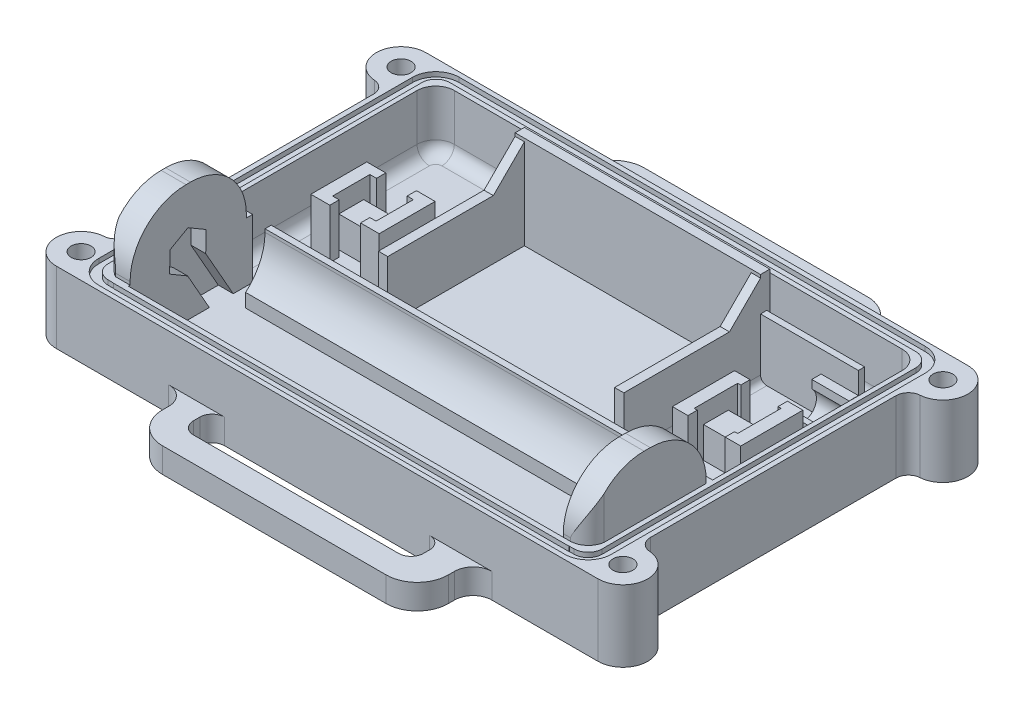
SolidWorks part; units mm, degrees
ref_plane "Спереди" through (0, 0, 0) normal (0, 0, 1) x (1, 0, 0)
ref_plane "Сверху" through (0, 0, 0) normal (0, 1, 0) x (1, 0, 0)
ref_plane "Справа" through (0, 0, 0) normal (1, 0, 0) x (0, 0, -1)
sketch "Эскиз1" plane through (0, 0, 0) normal (0, 1, 0) x (1, 0, 0)
  line L1 (-35, 9.5) -> (35, 9.5)
  line L2 (-35, 9.5) -> (-35, -9.5)
  line L3 (-35, -9.5) -> (35, -9.5)
  line L4 (35, 9.5) -> (35, -9.5)
  line L5 (-35, 9.5) -> (35, -9.5) construction
  line L6 (-35, -9.5) -> (35, 9.5) construction
  line L7 (-18.25, 37.5) -> (18.25, 37.5)
  line L8 (-18.25, 37.5) -> (-18.25, 10.5)
  line L9 (-18.25, 10.5) -> (18.25, 10.5)
  line L10 (18.25, 37.5) -> (18.25, 10.5)
  line L11 (-18.25, 37.5) -> (18.25, 10.5) construction
  line L12 (-18.25, 10.5) -> (18.25, 37.5) construction
  line L13 (-35, 44) -> (35, 44)
  line L14 (-35, 44) -> (-35, 38.5)
  line L15 (-35, 38.5) -> (35, 38.5)
  line L16 (35, 44) -> (35, 38.5)
  line L17 (-35, 44) -> (35, 38.5) construction
  line L18 (-35, 38.5) -> (35, 44) construction
  line L23 (-42, -12.5) -> (42, -12.5)
  line L24 (-42, -12.5) -> (-42, 47)
  line L25 (-42, 47) -> (42, 47)
  line L26 (42, -12.5) -> (42, 47)
  point P0 (0, 0)
  point P6 (0, 24)
  point P11 (0, 38.5)
  point P12 (0, 9.5)
  point P13 (0, 10.5)
  point P14 (0, 41.25)
  point P19 (0, 37.5)
  point P20 (-35, 0)
  point P25 (35, 0)
  point P26 (0, -9.5)
  point P27 (0, 44)
  dimension "D1" = 70
  dimension "D2" = 19
  dimension "D3" = 36.5
  dimension "D4" = 27
  dimension "D5" = 1
  dimension "D6" = 5.5
  dimension "D7" = 1
  dimension "D8" = 70
  dimension "D9" = 7
  dimension "D10" = 3
  dimension "D11" = 3
  dimension "D12" = 7
sketch "Эскиз7" plane through (0, 0, 0) normal (0, 1, 0) x (1, 0, 0)
  line L0 (-42.0364, 37.0159) -> (-42.0364, -2.5159)
  line L1 (-42, 47) -> (42, 47)
  line L2 (0, -12.5) -> (0, 47) construction
  line L3 (-42, -12.5) -> (42, -12.5)
  line L4 (42.0364, 37.0159) -> (42.0364, -2.5159)
  line L5 (-43.6, 47) -> (-42, 47)
  line L6 (36, 17.25) -> (-42.0364, 17.25) construction
  line L7 (43.6, 47) -> (42, 47)
  line L8 (43.6, -12.5) -> (42, -12.5)
  line L9 (-43.6, -12.5) -> (-42, -12.5)
  circle A0 centre (-43.6, 43) radius 1.6
  arc A1 (-43.6, 47) -> (-43.8909, 39.0106) centre (-43.6, 43) ccw
  arc A2 (-43.8909, 39.0106) -> (-42.0364, 37.0159) centre (-44.0364, 37.0159) cw
  arc A3 (43.8909, 39.0106) -> (42.0364, 37.0159) centre (44.0364, 37.0159) ccw
  arc A4 (43.6, 47) -> (43.8909, 39.0106) centre (43.6, 43) cw
  circle A5 centre (43.6, 43) radius 1.6
  circle A6 centre (43.6, -8.5) radius 1.6
  arc A7 (43.6, -12.5) -> (43.8909, -4.5106) centre (43.6, -8.5) ccw
  arc A8 (43.8909, -4.5106) -> (42.0364, -2.5159) centre (44.0364, -2.5159) cw
  arc A9 (-43.8909, -4.5106) -> (-42.0364, -2.5159) centre (-44.0364, -2.5159) ccw
  arc A10 (-43.6, -12.5) -> (-43.8909, -4.5106) centre (-43.6, -8.5) cw
  circle A11 centre (-43.6, -8.5) radius 1.6
  dimension "D1" = 3.2
  dimension "D2" = 8
  dimension "D3" = 2
extrude "Бобышка-Вытянуть4" add sketch "Эскиз7" along normal blind 2
sketch "Эскиз8" plane through (0, 2, 0) normal (0, 1, 0) x (1, 0, 0)
  line L0 (-43.6, -12.5) -> (43.6, -12.5) construction
  line L3 (43.6, 47) -> (-43.6, 47) construction
  line L4 (-43.6, -12.5) -> (43.6, -12.5)
  line L5 (42.0364, -2.5159) -> (42.0364, 37.0159)
  line L6 (-42.0364, -2.5159) -> (-42.0364, 37.0159)
  line L7 (43.6, 47) -> (-43.6, 47)
  line L9 (-36.0364, 44) -> (36.0364, 44)
  line L10 (-39.0364, 41) -> (-39.0364, -6.5)
  line L11 (-36.0364, -9.5) -> (36.0364, -9.5)
  line L12 (39.0364, 41) -> (39.0364, -6.5)
  arc A0 (42.0364, -2.5159) -> (43.8909, -4.5106) centre (44.0364, -2.5159) ccw construction
  circle A1 centre (43.6, -8.5) radius 1.6 construction
  arc A2 (43.6, -12.5) -> (43.8909, -4.5106) centre (43.6, -8.5) ccw construction
  circle A3 centre (-43.6, -8.5) radius 1.6 construction
  arc A4 (-43.8909, -4.5106) -> (-43.6, -12.5) centre (-43.6, -8.5) ccw construction
  arc A5 (-43.8909, -4.5106) -> (-42.0364, -2.5159) centre (-44.0364, -2.5159) ccw construction
  circle A6 centre (-43.6, 43) radius 1.6 construction
  circle A7 centre (43.6, 43) radius 1.6 construction
  arc A8 (43.8909, 39.0106) -> (42.0364, 37.0159) centre (44.0364, 37.0159) ccw construction
  arc A9 (43.8909, 39.0106) -> (43.6, 47) centre (43.6, 43) ccw construction
  arc A10 (-42.0364, 37.0159) -> (-43.8909, 39.0106) centre (-44.0364, 37.0159) ccw construction
  arc A11 (-43.6, 47) -> (-43.8909, 39.0106) centre (-43.6, 43) ccw construction
  arc A12 (42.0364, -2.5159) -> (43.8909, -4.5106) centre (44.0364, -2.5159) ccw
  circle A13 centre (43.6, -8.5) radius 1.6
  arc A14 (43.6, -12.5) -> (43.8909, -4.5106) centre (43.6, -8.5) ccw
  circle A15 centre (-43.6, -8.5) radius 1.6
  arc A16 (-43.8909, -4.5106) -> (-43.6, -12.5) centre (-43.6, -8.5) ccw
  arc A17 (-43.8909, -4.5106) -> (-42.0364, -2.5159) centre (-44.0364, -2.5159) ccw
  circle A18 centre (-43.6, 43) radius 1.6
  circle A19 centre (43.6, 43) radius 1.6
  arc A20 (43.8909, 39.0106) -> (42.0364, 37.0159) centre (44.0364, 37.0159) ccw
  arc A21 (43.8909, 39.0106) -> (43.6, 47) centre (43.6, 43) ccw
  arc A22 (-42.0364, 37.0159) -> (-43.8909, 39.0106) centre (-44.0364, 37.0159) ccw
  arc A23 (-43.6, 47) -> (-43.8909, 39.0106) centre (-43.6, 43) ccw
  arc A24 (36.0364, 44) -> (39.0364, 41) centre (36.0364, 41) cw
  arc A25 (36.0364, -9.5) -> (39.0364, -6.5) centre (36.0364, -6.5) ccw
  arc A26 (-39.0364, -6.5) -> (-36.0364, -9.5) centre (-36.0364, -6.5) ccw
  arc A27 (-36.0364, 44) -> (-39.0364, 41) centre (-36.0364, 41) ccw
  point P38 (0, 44)
  dimension "D5" = 3
  dimension "D1" = 3
  dimension "D2" = 3
  dimension "D3" = 3
  dimension "D4" = 3
extrude "Бобышка-Вытянуть5" add sketch "Эскиз8" along normal blind 9.5
sketch "Эскиз9" plane through (0, 11.5, 0) normal (0, 1, 0) x (1, 0, 0)
  line L0 (-42, 47) -> (42, 47) construction
  line L1 (-37.5, -11) -> (37.5, -11)
  line L2 (-40.5, -8) -> (-40.5, 42.5)
  line L3 (-37.5, 45.5) -> (37.5, 45.5)
  line L4 (40.5, -8) -> (40.5, 42.5)
  line L5 (-42, -12.5) -> (-42, 47) construction
  line L6 (42, -12.5) -> (42, 47) construction
  line L7 (-42, -12.5) -> (42, -12.5) construction
  arc A0 (-37.5, -11) -> (-40.5, -8) centre (-37.5, -8) cw
  arc A1 (-40.5, 42.5) -> (-37.5, 45.5) centre (-37.5, 42.5) cw
  arc A2 (37.5, 45.5) -> (40.5, 42.5) centre (37.5, 42.5) cw
  arc A3 (37.5, -11) -> (40.5, -8) centre (37.5, -8) ccw
  point P4 (0, 45.5)
  point P7 (-40.5, 17.25)
  point P10 (0, -11)
  dimension "D5" = 3
  dimension "D1" = 1.5
  dimension "D2" = 1.5
  dimension "D3" = 1.5
  dimension "D4" = 1.5
extrude "Вырез-Вытянуть-Тонкостенный1" cut sketch "Эскиз9" against normal blind 0.75 thin thin type mid plane wall 1.5
sketch "Эскиз10" plane through (0, 2, 0) normal (0, 1, 0) x (1, 0, 0)
  line L0 (-39.75, 42.5) -> (-39.75, -8) construction
  line L1 (-35, 9.5) -> (35, 9.5)
  line L2 (-35, 9.5) -> (-35, -9.5)
  line L3 (-35, -9.5) -> (35, -9.5)
  line L4 (35, 9.5) -> (35, -9.5)
  line L5 (-39.75, 10.5) -> (39.75, 10.5)
  line L6 (-39.75, 10.5) -> (-39.75, -7.6379)
  line L7 (-36.6026, -10.2814) -> (36.7169, -10.2814)
  line L8 (39.75, 10.5) -> (39.75, -7.2482)
  line L9 (36.7169, -10.2814) -> (39.75, -7.2482)
  line L10 (-36.6026, -10.2814) -> (-39.75, -7.6379)
extrude "Бобышка-Вытянуть6" add sketch "Эскиз10" along normal up to surface (9.5 mm away) up to face at (0, 11.5, -17.25)
sketch "Эскиз11" plane through (0, 11.5, 0) normal (0, 1, 0) x (1, 0, 0)
  line L1 (-35, 9.5) -> (-39, 9.5)
  line L2 (-35, 9.5) -> (-35, -9.216)
  line L3 (-35, -9.216) -> (-39, -9.216)
  line L4 (-39, 9.5) -> (-39, -9.216)
  line L5 (35, 9.5) -> (39, 9.5)
  line L6 (35, 9.5) -> (35, -9.4965)
  line L7 (35, -9.4965) -> (39, -9.4965)
  line L8 (39, 9.5) -> (39, -9.4965)
  point P5 (-39, 0.142)
  point P6 (-35, 0.142)
  dimension "D1" = 4
  dimension "D2" = 4
extrude "Бобышка-Вытянуть7" add sketch "Эскиз11" along normal blind 9.5
fillet "Скругление2" radius 9 4 edges at (-37, 21, -9.5) (37, 21, -9.5) (37, 21, 9.4965) (-37, 21, 9.216)
fillet "Скругление3" radius 9 2 edges at (0, 2, -9.5) (0, 2, 9.5)
sketch "Эскиз12" plane through (0, 2, 0) normal (0, 1, 0) x (1, 0, 0)
  line L0 (-19.75, 37.5) -> (-19.75, 38.5)
  line L1 (-18.25, 37.5) -> (18.25, 37.5)
  line L2 (-18.25, 37.5) -> (-18.25, 15.5)
  line L3 (19.75, 37.5) -> (35.5, 37.5)
  line L4 (18.25, 37.5) -> (18.25, 15.5)
  line L5 (-19.75, 38.5) -> (35.5, 38.5)
  line L8 (35.5, 38.5) -> (35.5, 37.5)
  line L9 (-19.75, 15.5) -> (-18.25, 15.5)
  line L10 (-18.25, 37.5) -> (-18.25, 15.5)
  line L11 (18.25, 15.5) -> (19.75, 15.5)
  line L12 (-19.75, 37.5) -> (-19.75, 15.5)
  line L13 (39.0364, 10.5) -> (-39.0364, 10.5) construction
  line L14 (-18.25, 37.5) -> (18.25, 37.5)
  line L15 (18.25, 37.5) -> (18.25, 15.5)
  line L17 (19.75, 37.5) -> (19.75, 15.5)
  point P1 (-18.25, 26.5)
  point P6 (18.25, 26.5)
  line M5 (-39.0364, 10.5) -> (39.0364, 10.5)
  dimension "D1" = 1.5
  dimension "D2" = 1.5
  dimension "D3" = 5
  dimension "D4" = 36.5
extrude "Бобышка-Вытянуть8" add sketch "Эскиз12" along normal up to surface (9.5 mm away) contours L17 L3 L8 L5 L12 L2 L1 L4 M5 region at (-19.1515, 2, -38) up to face at (0, 11.5, -32.0404)
sketch "Эскиз14" plane through (0, 2, 0) normal (0, 1, 0) x (1, 0, 0)
  line L0 (-29.125, 37.5) -> (-29.125, 10.5) construction
  line L1 (0, 37.5) -> (0, 10.5) construction
  line L2 (-25.625, 22) -> (-32.625, 22)
  line L4 (-25.625, 26) -> (-32.625, 26)
  line L5 (-32.625, 22) -> (-32.625, 26)
  line L6 (-25.625, 22) -> (-32.625, 26) construction
  line L7 (-25.625, 26) -> (-32.625, 22) construction
  line L8 (-18.25, 37.5) -> (18.25, 37.5) construction
  line L9 (-39, 24) -> (39, 24) construction
  line L10 (29.5663, 37.5) -> (29.5663, 10.5) construction
  line L11 (-18.25, 10.5) -> (18.25, 10.5) construction
  line L13 (-25.625, 26) -> (-25.625, 22)
  line L14 (26.0663, 26) -> (33.0663, 26)
  line L15 (26.0663, 26) -> (26.0663, 22)
  line L16 (26.0663, 22) -> (33.0663, 22)
  line L17 (33.0663, 26) -> (33.0663, 22)
  line L18 (26.0663, 26) -> (33.0663, 22) construction
  line L19 (26.0663, 22) -> (33.0663, 26) construction
  point P0 (-29.125, 24)
  point P4 (29.5663, 24)
  dimension "D1" = 4
  dimension "D2" = 7
  dimension "D3" = 7
  dimension "D4" = 4
extrude "Бобышка-Вытянуть9" add sketch "Эскиз14" along normal blind 5
fillet "Скругление4" radius 2 5 edges at (39.0364, 2, -25.75) (38.1577, 2, -43.1213) (-39.0364, 2, -25.75) (-38.1577, 2, -43.1213) (0, 2, -44)
sketch "Эскиз15" plane through (0, 2, 0) normal (0, 1, 0) x (1, 0, 0)
  line L2 (35.5, 37.5) -> (29.5, 37.5)
  line L3 (35.5, 37.5) -> (35.5, 31.5)
  line L4 (35.5, 31.5) -> (29.5, 31.5)
  line L5 (29.5, 37.5) -> (29.5, 31.5)
  dimension "D1" = 6
  dimension "D2" = 6
extrude "Бобышка-Вытянуть10" add sketch "Эскиз15" along normal blind 6
sketch "Эскиз16" plane through (29.5, 0, 0) normal (-1, 0, 0) x (0, 0, 1)
  line L0 (-37.5, 8) -> (-31.5, 8) construction
  line L1 (-33, 8) -> (-31.5, 8)
  line L2 (-36, 6.6771) -> (-36, 8)
  line L3 (-36, 8) -> (-33, 8)
  line L5 (-36, 6.5) -> (-33, 8) construction
  line L6 (-36, 8) -> (-33, 6.5) construction
  line L7 (-31.5, 8) -> (-31.5, 5.7989)
  line L8 (-31.5, 8) -> (-31.5, 2) construction
  line L9 (-31.5, 5.7989) -> (-32.3966, 5.7989)
  arc A0 (-36, 6.6771) -> (-32.3966, 5.7989) centre (-34.5, 5) ccw
  point P2 (-34.5, 7.25)
  dimension "D1" = 4.5
  dimension "D2" = 3
extrude "Вырез-Вытянуть1" cut sketch "Эскиз16" against normal up to next
sketch "Эскиз17" plane through (-35, 0, 0) normal (1, 0, 0) x (0, 0, -1)
  line L0 (0, 2) -> (0.142, 21) construction
  line L1 (0.5, 2) -> (-0.5, 2) construction
  line L2 (-0.216, 21) -> (0.5, 21) construction
  line L5 (2.9584, 9.8041) -> (2.9834, 13.1526)
  line L6 (2.9834, 13.1526) -> (0.096, 14.8485)
  line L7 (0.096, 14.8485) -> (-2.8164, 13.1959)
  line L8 (-2.8164, 13.1959) -> (-2.8414, 9.8474)
  line L9 (-2.8414, 9.8474) -> (0.046, 8.1515)
  line L10 (0.046, 8.1515) -> (3.2536, 2.4985)
  line L11 (2.9584, 9.8041) -> (6.1661, 4.1511)
  line L12 (3.2536, 2.4985) -> (6.1661, 4.1511)
  line L13 (0.046, 8.1515) -> (1.5022, 8.9778) [skipped]
  circle A0 centre (0.071, 11.5) radius 2.9 construction
  dimension "D1" = 5.8
extrude "Вырез-Вытянуть2" cut sketch "Эскиз17" against normal blind 2.4
sketch "Эскиз18" plane through (0, 11.5, 0) normal (0, 1, 0) x (1, 0, 0)
  line L0 (37.0364, 10.5) -> (-37.0364, 10.5) construction
  line L2 (-35, 9.5) -> (-35, 10.5)
  line L3 (-35, 10.5) -> (-32, 10.5)
  line L4 (-32, 9.5) -> (-32, 10.5)
  line L5 (35, 0.5) -> (-35, 0.5) construction
  line L6 (-35, 9.5) -> (-32, 9.5)
  line L7 (-35, 9.5) -> (-35, 0.5)
  line L8 (-35, 0.5) -> (-32, 0.5)
  line L9 (-32, 9.5) -> (-32, 6.3801)
  line L11 (-32, 6.3801) -> (35, 6.3801)
  line L12 (-35, 5) -> (-35, 0.5)
  line L13 (-35, 0.5) -> (35, 0.5)
  line L14 (35, 6.3801) -> (35, 0.5)
  line M2 (39.0364, 10.5) -> (-39.0364, 10.5)
  line M28 (-35, 9.5) -> (35, 9.5)
  dimension "D1" = 3
extrude "Вырез-Вытянуть3" cut sketch "Эскиз18" against normal up to surface (9.5 mm away) contours L14 L11 L9 L7 L8 L13 M28 | L4 L2 M28 M2 region at (-33.5, 11.5, -10) region at (-0.7448, 11.5, -3.5401) up to face at (0, 2, 0)
sketch "Эскиз19" plane through (0, 0.4934, 0.28) normal (0, 0.8697, 0.4935) x (1, 0, 0)
  line L1 (-37.4, 7.4115) -> (-35, 7.4115)
  line L2 (-37.4, 7.4115) -> (-37.4, 4.0628)
  line L3 (-37.4, 4.0628) -> (-35, 4.0628)
  line L4 (-35, 7.4115) -> (-35, 4.0628)
extrude "Вырез-Вытянуть4" cut sketch "Эскиз19" against normal up to surface (2.4732 mm away) up to face at (-5.3333, 2, -18.3479)
sketch "Эскиз20" plane through (35, 0, 0) normal (-1, 0, 0) x (0, 0, 1)
  line L0 (-0.0018, 21) -> (-0.0018, 2) construction
  line L1 (-0.5, 21) -> (0.4965, 21) construction
  line L2 (0.5, 2) -> (-6.3801, 2) construction
  line L3 (-6.3801, 4.1865) -> (-2.4666, 8.6738)
  line L4 (-6.3801, 4.1865) -> (-6.3801, 2)
  line L5 (-6.3801, 2) -> (-5.1223, 2)
  line L6 (-5.1223, 2) -> (-0.0018, 7.75)
  circle A0 centre (-0.0018, 11.5) radius 3.75
  line M1 (-6.3801, 4.1865) -> (-6.3801, 2)
  line M2 (-6.3801, 2) -> (0.5, 2)
  dimension "D1" = 7.5
extrude "Вырез-Вытянуть5" cut sketch "Эскиз20" against normal blind 3 contours L0 A0 | A0 L0 | A0 L3 L6 M1 M2 region at (35, 11.5, -1.5933) region at (35, 5.3437, -3.6924) region at (35, 11.5, 1.5898)
sketch "Эскиз22" plane through (0, 0, 0) normal (0, -1, 0) x (1, 0, 0)
  line L0 (0, 12.5) -> (0, -47) construction
  line L1 (-42, 12.5) -> (42, 12.5) construction
  line L2 (-42, -47) -> (42, -47) construction
  line L3 (-42, -17.25) -> (42, -17.25) construction
  line L4 (-42, 12.5) -> (-42, -47) construction
  line L5 (42, 12.5) -> (42, -47) construction
  line L6 (-18.5, -47) -> (18.5, -52) construction
  line L7 (-16.5, 17.5) -> (16.5, 17.5)
  line L8 (-18.5, 15.5) -> (-18.5, 14.5)
  line L9 (-16.5, 12.5) -> (16.5, 12.5)
  line L10 (18.5, 15.5) -> (18.5, 14.5)
  line L11 (-18.5, 17.5) -> (18.5, 12.5) construction
  line L12 (-18.5, 12.5) -> (18.5, 17.5) construction
  line L13 (-22.5, 11.5) -> (23.5, 11.5)
  line L14 (-22.5, 11.5) -> (-22.5, 16.5)
  line L15 (-17.5, 21.5) -> (18.5, 21.5)
  line L16 (23.5, 11.5) -> (23.5, 16.5)
  line L17 (-18.5, -52) -> (18.5, -47) construction
  line L18 (23.5, -46) -> (23.5, -51)
  line L19 (-17.5, -56) -> (18.5, -56)
  line L20 (-22.5, -46) -> (-22.5, -51)
  line L21 (-22.5, -46) -> (23.5, -46)
  line L22 (18.5, -50) -> (18.5, -49)
  line L23 (-16.5, -47) -> (16.5, -47)
  line L24 (-18.5, -50) -> (-18.5, -49)
  line L25 (-16.5, -52) -> (16.5, -52)
  arc A0 (16.5, 17.5) -> (18.5, 15.5) centre (16.5, 15.5) cw
  arc A1 (16.5, 12.5) -> (18.5, 14.5) centre (16.5, 14.5) ccw
  arc A2 (-18.5, 14.5) -> (-16.5, 12.5) centre (-16.5, 14.5) ccw
  arc A3 (-16.5, 17.5) -> (-18.5, 15.5) centre (-16.5, 15.5) ccw
  arc A4 (18.5, 21.5) -> (23.5, 16.5) centre (18.5, 16.5) cw
  arc A5 (-22.5, 16.5) -> (-17.5, 21.5) centre (-17.5, 16.5) cw
  arc A6 (-22.5, -51) -> (-17.5, -56) centre (-17.5, -51) ccw
  arc A7 (18.5, -56) -> (23.5, -51) centre (18.5, -51) ccw
  arc A8 (-16.5, -52) -> (-18.5, -50) centre (-16.5, -50) cw
  arc A9 (-18.5, -49) -> (-16.5, -47) centre (-16.5, -49) cw
  arc A10 (16.5, -47) -> (18.5, -49) centre (16.5, -49) cw
  arc A11 (16.5, -52) -> (18.5, -50) centre (16.5, -50) ccw
  point P12 (0, 15)
  point P29 (0, 12.5)
  point P34 (0, 17.5)
  point P63 (0, -49.5)
  dimension "D3" = 2
  dimension "D8" = 5
  dimension "D1" = 37
  dimension "D2" = 5
  dimension "D4" = 1
  dimension "D5" = 5
  dimension "D6" = 4
  dimension "D7" = 4
extrude "Бобышка-Вытянуть11" add sketch "Эскиз22" against normal blind 4
fillet "Скругление6" radius 3 4 edges at (-22.5, 2, -47) (23.5, 2, -47) (-22.5, 2, 12.5) (23.5, 2, 12.5)
sketch "Эскиз23" plane through (0, 2, 0) normal (0, 1, 0) x (1, 0, 0)
  line L0 (-31.5667, 28.5) -> (-31.5667, 27)
  line L1 (-32.625, 27) -> (-31.5667, 27)
  line L2 (-32.625, 27) -> (-32.625, 21)
  line L3 (-32.625, 21) -> (-31.5667, 21)
  line L4 (-25.625, 27) -> (-25.625, 21)
  line L5 (-32.625, 27) -> (-25.625, 21) construction
  line L6 (-32.625, 21) -> (-25.625, 27) construction
  line L7 (-34.625, 28.5) -> (-31.5667, 28.5)
  line L8 (-34.625, 28.5) -> (-34.625, 19.5)
  line L9 (-34.625, 19.5) -> (-31.5667, 19.5)
  line L10 (-23.625, 28.5) -> (-23.625, 19.5)
  line L11 (-34.625, 28.5) -> (-23.625, 19.5) construction
  line L12 (-34.625, 19.5) -> (-23.625, 28.5) construction
  line L13 (-26.625, 28.5) -> (-26.625, 27)
  line L14 (-31.5667, 21) -> (-31.5667, 19.5)
  line L15 (-26.625, 21) -> (-26.625, 19.5)
  line L16 (-26.625, 27) -> (-25.625, 27)
  line L17 (-26.625, 28.5) -> (-23.625, 28.5)
  line L18 (-26.625, 21) -> (-25.625, 21)
  line L19 (-26.625, 19.5) -> (-23.625, 19.5)
  line L20 (26.5663, 29.004) -> (26.5663, 27.5)
  line L21 (26.0663, 27.5) -> (26.5663, 27.5)
  line L22 (26.0663, 27.5) -> (26.0663, 20.5)
  line L23 (26.0663, 20.5) -> (26.5663, 20.5)
  line L24 (33.0663, 27.5) -> (33.0663, 20.5)
  line L25 (26.0663, 27.5) -> (33.0663, 20.5) construction
  line L26 (26.0663, 20.5) -> (33.0663, 27.5) construction
  line L27 (24.0663, 29.004) -> (26.5663, 29.004)
  line L28 (24.0663, 29.004) -> (24.0663, 18.996)
  line L29 (24.0663, 18.996) -> (26.5663, 18.996)
  line L30 (35.0663, 29.004) -> (35.0663, 18.996)
  line L31 (24.0663, 29.004) -> (35.0663, 18.996) construction
  line L32 (24.0663, 18.996) -> (35.0663, 29.004) construction
  line L33 (32.5663, 29.004) -> (32.5663, 27.5)
  line L34 (32.5663, 29.004) -> (35.0663, 29.004)
  line L35 (32.5663, 27.5) -> (33.0663, 27.5)
  line L36 (26.5663, 20.5) -> (26.5663, 18.996)
  line L37 (32.5663, 20.5) -> (32.5663, 18.996)
  line L38 (32.5663, 20.5) -> (33.0663, 20.5)
  line L39 (32.5663, 18.996) -> (35.0663, 18.996)
  point P0 (-29.125, 24)
  point P5 (0, 0)
  point P6 (-29.125, 24)
  point P17 (29.5663, 24)
  point P25 (29.5663, 24)
  point P37 (-34.625, 24)
  point P38 (-32.625, 24)
  point P39 (-25.625, 24)
  point P40 (0, 0)
  dimension "D1" = 6
  dimension "D3" = 7
  dimension "D4" = 3.5
  dimension "D5" = 2
  dimension "D6" = 7
  dimension "D7" = 0.5
  dimension "D8" = 0.5
  dimension "D9" = 2
extrude "Бобышка-Вытянуть12" add sketch "Эскиз23" along normal blind 8
chamfer "Фаска1" distance 1.3 angle 45 4 edges at (43.6, 0, -44.6) (43.6, 0, 10.1) (-43.6, 0, 6.9) (-43.6, 0, -41.4)
fillet "Скругление7" radius 1 2 edges at (-19.75, 2, -27) (19.75, 2, -26.5)
sketch "Эскиз24" plane through (0, 11.5, 0) normal (0, 1, 0) x (1, 0, 0)
  line L0 (-42, 17.25) -> (42, 17.25) construction
  line L1 (-42, -12.5) -> (-42, 47) construction
  line L2 (42, -12.5) -> (42, 47) construction
  line L3 (-39.0364, -6.5) -> (-40.4068, -6.5)
  line L4 (-40.4068, -6.5) -> (-40.4068, -10.3692)
  line L5 (-40.4068, -10.3692) -> (-36.0364, -10.2814)
  line L6 (-36.6026, -10.2814) -> (36.7169, -10.2814) construction
  line L7 (-36.0364, -10.2814) -> (-36.0364, -9.5)
  line L8 (39.0364, -6.5) -> (40.5092, -6.5)
  line L9 (40.5092, -6.5) -> (40.5092, -11.3779)
  line L10 (40.5092, -11.3779) -> (36.0364, -11.3779)
  line L11 (36.0364, -11.3779) -> (36.0364, -9.5)
  arc A2 (39.0364, -6.5) -> (36.0364, -9.5) centre (36.0364, -6.5) cw
  arc A3 (-36.0364, -9.5) -> (-39.0364, -6.5) centre (-36.0364, -6.5) cw
  arc A4 (-41.25, -8) -> (-37.5, -11.75) centre (-37.5, -8) ccw construction
extrude "Вырез-Вытянуть6" cut sketch "Эскиз24" along normal through all
sketch "Эскиз25" plane through (0, 2, 0) normal (0, 1, 0) x (1, 0, 0)
  line L0 (35, 44) -> (35, 38.5) construction
  line L1 (-35, 37.5) -> (35, 37.5)
  line L2 (-35, 37.5) -> (-35, 39)
  line L3 (-35, 39) -> (35, 39)
  line L4 (35, 37.5) -> (35, 39)
  dimension "D1" = 1.5
sketch "Эскиз26" plane through (0, 2, 0) normal (0, 1, 0) x (1, 0, 0)
  line L0 (-19.75, 38.5) -> (-19.75, 15.5) construction
  line L1 (19.75, 37.5) -> (-19.75, 37.5)
  line L2 (19.75, 37.5) -> (19.75, 39)
  line L3 (19.75, 39) -> (-19.75, 39)
  line L4 (-19.75, 37.5) -> (-19.75, 39)
  point P5 (0, 0)
  dimension "D1" = 1.5
extrude "Бобышка-Вытянуть14" add sketch "Эскиз26" along normal blind 15
chamfer "Фаска2" distance 5 angle 45 2 edges at (-19, 11.5, -37.5) (19, 11.5, -37.5)
